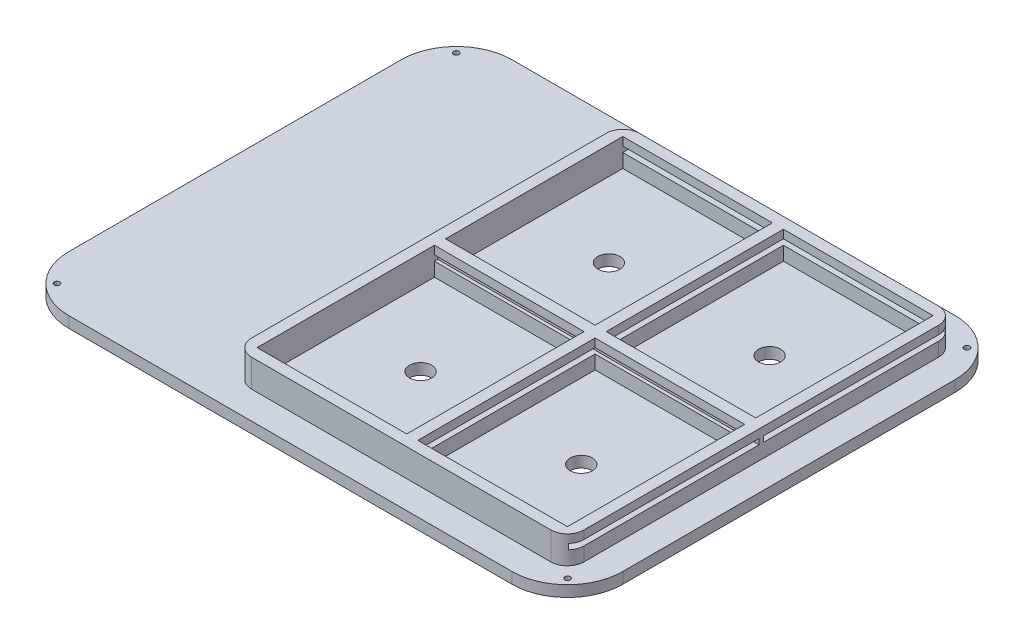
SolidWorks part; units mm, degrees
ref_plane "Front Plane" through (0, 0, 0) normal (0, 0, 1) x (1, 0, 0)
ref_plane "Top Plane" through (0, 0, 0) normal (0, 1, 0) x (1, 0, 0)
ref_plane "Right Plane" through (0, 0, 0) normal (1, 0, 0) x (0, 0, -1)
sketch "Sketch1" plane through (0, 0, 0) normal (0, 1, 0) x (1, 0, 0)
  line L1 (0, 0) -> (127, 0)
  line L2 (0, 0) -> (0, 101.6)
  line L3 (0, 101.6) -> (127, 101.6)
  line L4 (127, 0) -> (127, 101.6)
  dimension "D1" = 127
  dimension "D2" = 101.6
extrude "Boss-Extrude1" add sketch "Sketch1" along normal blind 2.54
sketch "Sketch2" plane through (0, 2.54, 0) normal (0, 1, 0) x (1, 0, 0)
  line L0 (44.45, 95.25) -> (44.45, 6.35)
  line L1 (46.99, 92.71) -> (46.99, 52.07)
  line L2 (46.99, 8.89) -> (81.28, 8.89)
  line L3 (118.11, 8.89) -> (118.11, 49.53)
  line L4 (118.11, 92.71) -> (83.82, 92.71)
  line L5 (81.28, 49.53) -> (46.99, 49.53)
  line L6 (81.28, 52.07) -> (46.99, 52.07)
  line L7 (118.11, 52.07) -> (83.82, 52.07)
  line L10 (81.28, 92.71) -> (81.28, 52.07)
  line L13 (44.45, 6.35) -> (120.65, 6.35)
  line L14 (120.65, 6.35) -> (120.65, 95.25)
  line L15 (120.65, 95.25) -> (44.45, 95.25)
  line L16 (118.11, 49.53) -> (83.82, 49.53)
  line L17 (83.82, 92.71) -> (83.82, 52.07)
  line L18 (81.28, 92.71) -> (46.99, 92.71)
  line L19 (118.11, 92.71) -> (46.99, 92.71) construction
  line L20 (83.82, 8.89) -> (118.11, 8.89)
  line L21 (118.11, 52.07) -> (118.11, 92.71)
  line L22 (118.11, 8.89) -> (118.11, 92.71) construction
  line L23 (46.99, 8.89) -> (118.11, 8.89) construction
  line L24 (81.28, 49.53) -> (81.28, 8.89)
  line L25 (46.99, 49.53) -> (46.99, 8.89)
  line L26 (46.99, 92.71) -> (46.99, 8.89) construction
  line L27 (83.82, 49.53) -> (83.82, 8.89)
  line L28 (0, 101.6) -> (0, 0) construction
  dimension "D2" = 44.45
  dimension "D1" = 2.54
  dimension "D3" = 76.2
extrude "Boss-Extrude2" add sketch "Sketch2" along normal blind 6.35
sketch "Sketch3" plane through (0, 2.54, 0) normal (0, 1, 0) x (1, 0, 0)
  line L0 (64.135, 92.71) -> (64.135, 52.07) construction
  line L3 (100.965, 92.71) -> (100.965, 52.07) construction
  line L4 (118.11, 92.71) -> (83.82, 92.71) construction
  line L5 (83.82, 52.07) -> (118.11, 52.07) construction
  line L6 (100.965, 8.89) -> (100.965, 49.53) construction
  line L7 (83.82, 8.89) -> (118.11, 8.89) construction
  line L8 (118.11, 49.53) -> (83.82, 49.53) construction
  line L9 (64.135, 8.89) -> (64.135, 49.53) construction
  line L10 (46.99, 8.89) -> (81.28, 8.89) construction
  line L11 (81.28, 49.53) -> (46.99, 49.53) construction
  line L12 (81.28, 92.71) -> (46.99, 92.71) construction
  line L13 (46.99, 52.07) -> (81.28, 52.07) construction
  circle A0 centre (64.135, 72.39) radius 2.54
  circle A1 centre (100.965, 72.39) radius 2.54
  circle A2 centre (64.135, 29.21) radius 2.54
  circle A4 centre (100.965, 29.21) radius 2.54
extrude "Cut-Extrude1" cut sketch "Sketch3" against normal through all
sketch "Sketch4" plane through (120.65, 0, 0) normal (1, 0, 0) x (0, 0, -1)
  line L0 (95.25, 8.89) -> (95.25, 6.982)
  line L1 (93.98, 5.715) -> (51.308, 5.715)
  line L2 (95.25, 8.89) -> (95.25, 2.54) construction
  line L3 (95.25, 6.982) -> (95.25, 5.715)
  line L4 (95.25, 5.715) -> (93.98, 5.715)
  line L5 (93.98, 5.715) -> (93.98, 6.982)
  line L6 (93.98, 6.982) -> (51.308, 6.982)
  line L7 (51.308, 6.982) -> (51.308, 5.715)
  line L8 (50.8, 8.89) -> (50.8, 2.54)
  line L9 (6.35, 8.89) -> (95.25, 8.89) construction
  line L10 (6.35, 2.54) -> (95.25, 2.54) construction
  line L11 (7.62, 5.715) -> (7.62, 6.982)
  line L12 (50.292, 6.982) -> (50.292, 5.715)
  line L13 (7.62, 5.715) -> (50.292, 5.715)
  line L14 (7.62, 6.982) -> (50.292, 6.982)
  dimension "D1" = 1.27
  dimension "D2" = 42.672
extrude "Cut-Extrude2" cut sketch "Sketch4" against normal up to surface (73.66 mm away) contours L11 L14 L12 L13 | L1 L7 L6 L5 up to face at (46.99, 5.715, -29.21)
fillet "Fillet1" radius 3.81 4 edges at (120.65, 5.715, -95.25) (120.65, 5.715, -6.35) (44.45, 5.715, -6.35) (44.45, 5.715, -95.25)
fillet "Fillet2" radius 12.7 4 edges at (127, 1.27, -101.6) (127, 1.27, 0) (0, 1.27, 0) (0, 1.27, -101.6)
sketch "Sketch5" plane through (0, 2.54, 0) normal (0, 1, 0) x (1, 0, 0)
  line L0 (0, 50.8) -> (127, 50.8) construction
  line L1 (0, 88.9) -> (0, 12.7) construction
  line L2 (127, 12.7) -> (127, 88.9) construction
  line L3 (63.5, 101.6) -> (63.5, 0) construction
  line L4 (114.3, 101.6) -> (12.7, 101.6) construction
  line L5 (12.7, 0) -> (114.3, 0) construction
  circle A0 centre (4.9632, 5.0241) radius 0.635
  circle A1 centre (122.0368, 5.0241) radius 0.635
  circle A2 centre (122.0368, 96.5759) radius 0.635
  circle A3 centre (4.9632, 96.5759) radius 0.635
extrude "Cut-Extrude3" cut sketch "Sketch5" against normal through all
